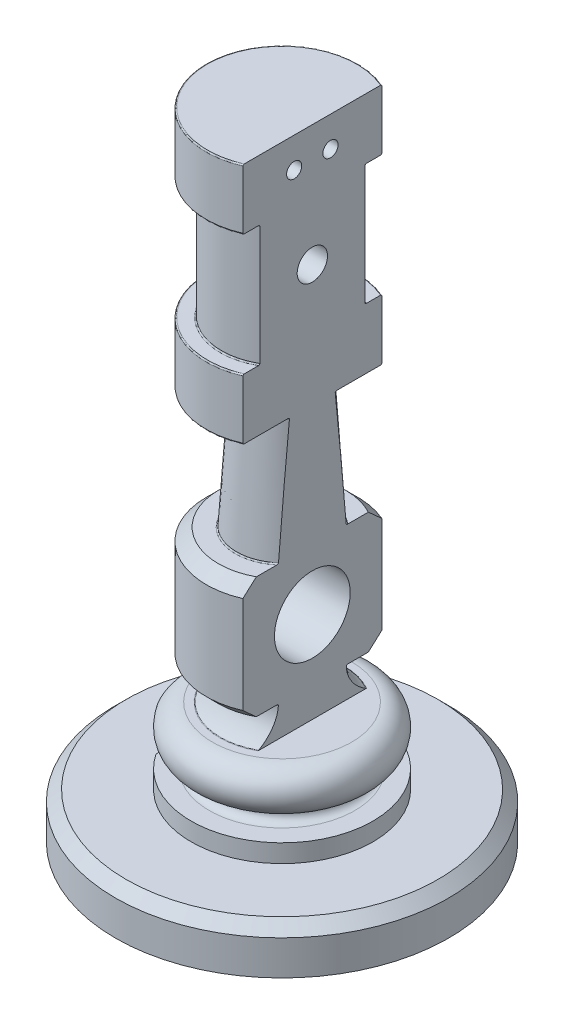
SolidWorks part; units mm, degrees
material "Gray Cast Iron"
ref_plane "Front Plane" through (0, 0, 0) normal (0, 0, 1) x (1, 0, 0)
ref_plane "Top Plane" through (0, 0, 0) normal (0, 1, 0) x (1, 0, 0)
ref_plane "Right Plane" through (0, 0, 0) normal (1, 0, 0) x (0, 0, -1)
sketch "Sketch1" plane through (0, 0, 0) normal (1, 0, 0) x (0, 0, -1)
  line L0 (0, -126.0334) -> (0, 6175.6351) construction
  line L1 (-7.9375, 44.45) -> (0, 44.45)
  line L2 (-7.9375, 44.45) -> (-7.9375, 38.1)
  line L3 (-7.9375, 38.1) -> (-6.35, 38.1)
  line L4 (-6.35, 38.1) -> (-6.35, 25.4)
  line L5 (-6.35, 25.4) -> (-7.9375, 25.4)
  line L6 (-7.9375, 25.4) -> (-7.9375, 19.05)
  line L7 (-7.9375, 19.05) -> (-3.9688, 19.05)
  line L8 (-3.9688, 19.05) -> (-4.7625, 6.35)
  line L9 (-4.7625, 6.35) -> (-7.9375, 6.35)
  line L10 (-7.9375, 6.35) -> (-7.9375, -6.35)
  line L11 (-7.9375, -6.35) -> (-4.7625, -6.35)
  line L12 (-6.477, -9.532) -> (-7.2918, -9.532)
  line L13 (-7.6213, -15.5746) -> (-9.525, -15.5746)
  line L14 (-9.525, -15.5746) -> (-9.525, -17.4625)
  line L15 (-9.525, -17.4625) -> (-4.7625, -17.4625)
  line L16 (0, 44.45) -> (0, -22.225)
  line L17 (-4.7625, -17.4625) -> (-4.7625, -22.225)
  line L18 (-4.7625, -22.225) -> (0, -22.225)
  arc A0 (-4.7625, -6.35) -> (-6.477, -9.532) centre (-8.5725, -6.35) cw
  arc A1 (-7.2918, -9.532) -> (-7.535, -13.9918) centre (-7.2918, -11.7685) ccw
  arc A2 (-7.535, -13.9918) -> (-7.6213, -15.5746) centre (-7.6213, -14.7808) cw
  point P5 (-7.9375, 0)
  point P22 (-9.525, -11.6467)
  dimension "D15" = 3.81
  dimension "D19" = 19.05
  dimension "D22" = 9.525
  dimension "D16" = 0.7937
  dimension "D2" = 6.35
  dimension "D3" = 12.7
  dimension "D4" = 12.7
  dimension "D5" = 15.875
  dimension "D6" = 6.35
  dimension "D7" = 15.875
  dimension "D8" = 12.7
  dimension "D9" = 7.9375
  dimension "D10" = 9.525
  dimension "D11" = 12.7
  dimension "D12" = 15.875
  dimension "D13" = 9.525
  dimension "D14" = 12.954
  dimension "D17" = 19.05
  dimension "D18" = 1.8879
  dimension "D20" = 11.1125
  dimension "D21" = 15.07
  dimension "D23" = 4.7625
revolve "Revolve1" add sketch "Sketch1" angle 360 about L0
sketch "Sketch2" plane through (0, 0, 0) normal (1, 0, 0) x (0, 0, -1)
  line L0 (-4.7625, -22.225) -> (-17.4625, -22.225)
  line L1 (-4.7625, -22.225) -> (4.7625, -22.225) construction
  line L2 (-17.4625, -22.225) -> (-17.4625, -18.585)
  line L3 (-17.4625, -18.585) -> (-16.34, -17.4625)
  line L4 (-16.34, -17.4625) -> (-4.7625, -17.4625)
  line L5 (-9.525, -17.4625) -> (9.525, -17.4625) construction
  line L6 (-4.7625, -17.4625) -> (-4.7625, -22.225)
  line L7 (0, 26.5926) -> (0, -26.5926) construction
  point P13 (0, 0)
  dimension "D1" = 34.925
  dimension "D2" = 45
  dimension "D3" = 1.5875
  dimension "D4" = 9.525
revolve "Revolve2" add sketch "Sketch2" angle 360 about L7
sketch "Sketch3" plane through (0, 44.45, 0) normal (0, 1, 0) x (1, 0, 0)
  line L0 (0, 0) -> (-9.5283, 0)
  line L1 (3.1717, 12.065) -> (10.7917, 12.065)
  line L2 (3.1717, 12.065) -> (3.1717, -10.5994)
  line L3 (3.1717, -10.5994) -> (10.7917, -10.5994)
  line L4 (10.7917, 12.065) -> (10.7917, -10.5994)
  circle A1 centre (0, 0) radius 9.5283 construction
  circle M3 centre (0, 0) radius 7.9375
  dimension "D1" = 12.7
  dimension "D2" = 7.62
extrude "Cut-Extrude2" cut sketch "Sketch3" along direction (0, 1, 0) on the side against the normal up to surface (53.982 mm away) contours L2 M3 | L4 L1 L2 L3 M3
sketch "Sketch4" plane through (0, -17.4625, 0) normal (0, 1, 0) x (1, 0, 0)
  line L0 (0, 0) -> (9.5283, 0)
  line L1 (-7.9342, 12.7) -> (-13.5222, 12.7)
  line L2 (-7.9342, 12.7) -> (-7.9342, -12.7)
  line L3 (-7.9342, -12.7) -> (-13.5222, -12.7)
  line L4 (-13.5222, 12.7) -> (-13.5222, -12.7)
  circle A0 centre (0, 0) radius 9.5283 construction
  point P9 (-7.9342, 0)
  dimension "D1" = 17.4625
  dimension "D2" = 5.588
  dimension "D3" = 25.4
extrude "Cut-Extrude3" cut sketch "Sketch4" along normal up to surface (7.9305 mm away) contours L4 L3 L2 L1 up to face at (-1.6527, -9.532, 0)
sketch "Sketch5" plane through (3.1717, 0, 0) normal (1, 0, 0) x (0, 0, -1)
  line L1 (7.2763, 38.1) -> (5.5012, 38.1) construction
  line L2 (7.2763, 44.45) -> (-7.2763, 44.45) construction
  circle A0 centre (0, 31.75) radius 1.5875
  circle A1 centre (-1.9031, 41.275) radius 0.7937
  circle A2 centre (1.9031, 41.275) radius 0.7937
  circle A3 centre (0, 0) radius 3.9688
  dimension "D1" = 3.175
  dimension "D3" = 1.5875
  dimension "D7" = 7.9375
  dimension "D2" = 6.35
  dimension "D4" = 3.8062
  dimension "D5" = 1.9031
  dimension "D6" = 3.175
extrude "Cut-Extrude4" cut sketch "Sketch5" against normal blind 49.53 contours A2 | A1 | A0 | A3
sketch "Sketch6" plane through (3.1717, 0, 0) normal (1, 0, 0) x (0, 0, -1)
  circle A0 centre (0, 31.75) radius 3.175
  dimension "D1" = 6.35
extrude "Cut-Extrude5" cut sketch "Sketch6" against normal blind 49.53 from offset 6.096 offset against normal yes
chamfer "Chamfer4" distance 1.27 angle 45 2 edges at (-7.9375, -6.35, 0) (-7.9375, 6.35, 0)
fillet "Fillet1" radius 0.127 10 edges at (-6.477, -9.532, 0) (-4.7625, -6.35, 0) (-7.9375, 38.1, 0) (-6.35, 38.1, 0) (-6.35, 25.4, 0) (-7.9375, 25.4, 0) (-7.9375, 19.05, 0) (-3.9687, 19.05, 0) (-4.7625, 6.35, 0) (-7.9375, 44.45, 0)
